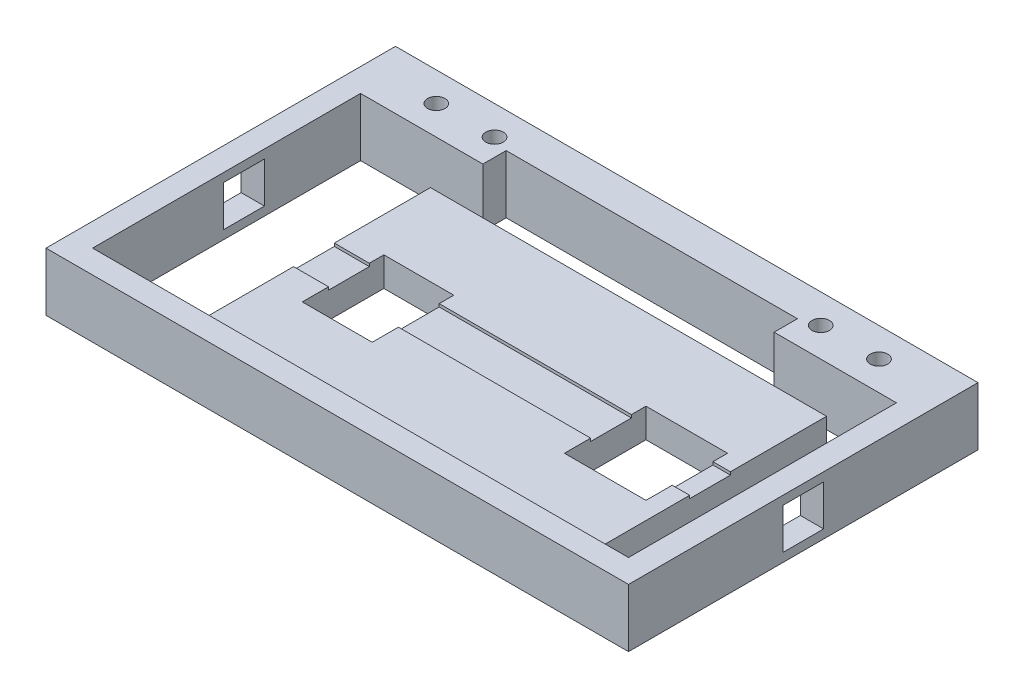
SolidWorks part; units mm, degrees
note: The reader was unsure of these and kept them because the rebuilt part matched: shared geometry of "Croquis1<2>".
ref_plane "Alzado" through (0, 0, 0) normal (0, 0, 1) x (1, 0, 0)
ref_plane "Planta" through (0, 0, 0) normal (0, 1, 0) x (1, 0, 0)
ref_plane "Vista lateral" through (0, 0, 0) normal (1, 0, 0) x (0, 0, -1)
sketch "Croquis1" plane through (0, 0, 0) normal (0, 1, 0) x (1, 0, 0)
  line L0 (-25, 20) -> (-25, 24)
  line L1 (-50, 30) -> (50, 30)
  line L2 (-50, 30) -> (-50, -30)
  line L3 (-50, -30) -> (50, -30)
  line L4 (50, 30) -> (50, -30)
  line L5 (-50, 30) -> (50, -30) construction
  line L6 (-50, -30) -> (50, 30) construction
  line L7 (-46, 20) -> (46, 20)
  line L8 (-46, 20) -> (-46, -26)
  line L9 (-46, -26) -> (46, -26)
  line L10 (46, 20) -> (46, -26)
  line L11 (-25, 24) -> (25, 24)
  line L12 (25, 24) -> (25, 20)
  circle A0 centre (-38, 25) radius 1.5
  circle A1 centre (-28, 25) radius 1.5
  circle A2 centre (28, 25) radius 1.5
  circle A3 centre (38, 25) radius 1.5
  point P0 (0, 0)
  point P6 (0, 0)
  point P19 (0, 24)
  dimension "D10" = 3
  dimension "D11" = 3
  dimension "D12" = 3
  dimension "D13" = 3
  dimension "D1" = 100
  dimension "D2" = 60
  dimension "D3" = 10
  dimension "D4" = 4
  dimension "D5" = 4
  dimension "D6" = 4
  dimension "D7" = 12
  dimension "D8" = 10
  dimension "D9" = 5
  dimension "D14" = 12
  dimension "D15" = 10
  dimension "D16" = 50
  dimension "D17" = 50
extrude "Saliente-Extruir1" add sketch "Croquis1" along normal blind 10 contours L4 L1 L2 L3 A3 A2 A1 A0 L11 L12 L7 L10 L9 L8 L0
extrude "Saliente-Extruir2" add sketch "Croquis1<2>" against normal blind 3 and the other way blind 2 contours L10 L7 L8 L9
sketch "Croquis1<2>" plane through (0, 0, 0) normal (0, 1, 0) x (1, 0, 0) same geometry as "Croquis1"
sketch "Croquis2" plane through (0, 2, 0) normal (0, 1, 0) x (1, 0, 0)
  line L1 (-28, 6) -> (-16, 6)
  line L2 (-28, 6) -> (-28, -8)
  line L3 (-28, -8) -> (-16, -8)
  line L4 (-16, 6) -> (-16, -8)
  line L5 (-28, 6) -> (-16, -8) construction
  line L6 (-28, -8) -> (-16, 6) construction
  line L7 (17, 6) -> (31, 6)
  line L8 (17, 6) -> (17, -8)
  line L9 (17, -8) -> (31, -8)
  line L10 (31, 6) -> (31, -8)
  line L11 (17, 6) -> (31, -8) construction
  line L12 (17, -8) -> (31, 6) construction
  line L16 (-25, 24) -> (25, 24) construction
  point P0 (-22, -1)
  point P5 (24, -1)
  dimension "D3" = 14
  dimension "D1" = 12
  dimension "D2" = 14
  dimension "D4" = 17
  dimension "D5" = 18
  dimension "D6" = 16
extrude "Cortar-Extruir1" cut sketch "Croquis2" against normal up to surface (5 mm away) up to face at (0, -3, 3)
sketch "Croquis3" plane through (0, 2, 0) normal (0, 1, 0) x (1, 0, 0)
  line L6 (34, 20) -> (34, -26)
  line L12 (46, -26) -> (46, 20)
  line L13 (46, 20) -> (25, 20)
  line L14 (25, 20) -> (-25, 20)
  line L15 (-25, 20) -> (-46, 20)
  line L16 (-46, 20) -> (-46, -26)
  line L17 (-46, -26) -> (46, -26)
  line L18 (46, -26) -> (46, 20)
  line L19 (46, 20) -> (34, 20)
  line L23 (34, -26) -> (46, -26)
  dimension "D2" = 12
  dimension "D1" = 0
extrude "Cortar-Extruir2" cut sketch "Croquis3" against normal up to surface (5 mm away)
pattern_linear "MatrizL1" count 2 spacing 80 along (-1, 0, 0) of "Cortar-Extruir2"
sketch "Croquis4" plane through (46, 0, 0) normal (-1, 0, 0) x (0, 0, 1)
  line L1 (3.5, 8.5) -> (-3.5, 8.5)
  line L2 (3.5, 8.5) -> (3.5, 1.5)
  line L3 (3.5, 1.5) -> (-3.5, 1.5)
  line L4 (-3.5, 8.5) -> (-3.5, 1.5)
  line L5 (3.5, 8.5) -> (-3.5, 1.5) construction
  line L6 (3.5, 1.5) -> (-3.5, 8.5) construction
  line L7 (-30, 10) -> (30, 10) construction
  line L8 (30, 10) -> (30, 0) construction
  point P0 (0, 5)
  point P5 (0, 0)
  point P6 (0.8484, 4.745)
  point P9 (0, 0)
  point P10 (0, 0)
  point P11 (0, 10)
  point P14 (30, 5)
  dimension "D1" = 7
  dimension "D2" = 7
extrude "Cortar-Extruir3" cut sketch "Croquis4" against normal up to surface (100 mm away)
pattern_linear "MatrizL2" count 2 spacing 96 along (-1, 0, 0) of "Cortar-Extruir3"
